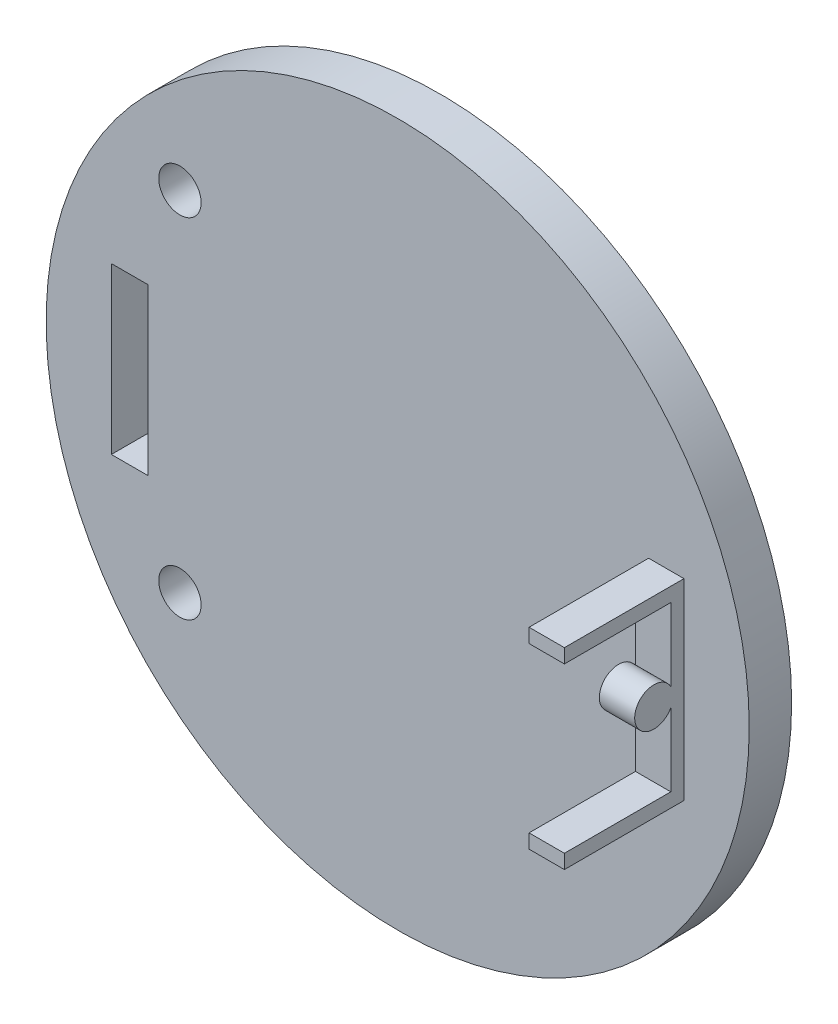
SolidWorks part; units mm, degrees
ref_plane "Front Plane" through (0, 0, 0) normal (0, 0, 1) x (1, 0, 0)
ref_plane "Top Plane" through (0, 0, 0) normal (0, 1, 0) x (1, 0, 0)
ref_plane "Right Plane" through (0, 0, 0) normal (1, 0, 0) x (0, 0, -1)
sketch "Sketch1" plane through (0, 0, 0) normal (0, 0, 1) x (1, 0, 0)
  line L0 (-1000, 0) -> (49000, 0) construction
  line L1 (17.755, 6.8) -> (20.255, 6.8)
  line L2 (17.755, 6.8) -> (17.755, -6.8)
  line L3 (17.755, -6.8) -> (20.255, -6.8)
  line L4 (20.255, 6.8) -> (20.255, -6.8)
  circle A0 centre (0, 0) radius 24.875
  point P7 (20.255, 0)
  point P10 (24.875, 0)
  dimension "D1" = 49.75
  dimension "D2" = 6.8
  dimension "D3" = 6.8
  dimension "D4" = 20.255
  dimension "D5" = 2.5
sketch "Sketch2" plane through (0, 0, 0) normal (0, 0, 1) x (1, 0, 0)
extrude "Boss-Extrude2" add sketch "Sketch1" against normal blind 3 contours A0
extrude "Boss-Extrude3" add sketch "Sketch1<4>" along normal blind 8.46 contours L2 L3 L4 L1
sketch "Sketch1<4>" plane through (0, 0, 0) normal (0, 0, 1) x (1, 0, 0) same geometry as "Sketch1"
sketch "Sketch4" plane through (20.255, 0, 0) normal (1, 0, 0) x (0, 0, -1)
  line L0 (0, 6.8) -> (0, 0.65)
  line L1 (0, 6.8) -> (0, -6.8) construction
  line L2 (0, -0.65) -> (0, -6.8)
  line L3 (0, 24.875) -> (0, -24.875) construction
  line L7 (0, 0.65) -> (-0.9313, 0.65) construction
  line L8 (-0.9313, 0.65) -> (-0.9313, -0.65) construction
  line L9 (-0.9313, -0.65) -> (0, -0.65) construction
  line L10 (-0.9313, 0.65) -> (0, 0.65)
  line L11 (-0.9313, -0.65) -> (0, -0.65)
  line L12 (0, 6.8) -> (-8.46, 6.8)
  line L13 (-8.46, 6.8) -> (-8.46, 5.8)
  line L14 (-8.46, 6.8) -> (-8.46, -6.8) construction
  line L15 (-8.46, 5.8) -> (-0.9313, 5.8)
  line L16 (-0.9313, 5.8) -> (-0.9313, 0.65)
  line L17 (-0.9313, -0.65) -> (-0.9313, -5.8)
  line L19 (-0.9313, -5.8) -> (-8.46, -5.8)
  line L20 (-8.46, -5.8) -> (-8.46, -6.8)
  line L21 (-8.46, -6.8) -> (0, -6.8)
  arc A4 (-0.9313, -0.65) -> (-0.9313, 0.65) centre (-2.1259, 0) cw
  point P15 (-0.9313, 0)
  line M8 (-8.46, 6.8) -> (-8.46, -6.8)
  dimension "D1" = 0.65
  dimension "D2" = 1.36
  dimension "D3" = 1
  dimension "D4" = 1
extrude "Cut-Extrude1" cut sketch "Sketch4" against normal up to surface (2.5 mm away) contours L17 A4 L16 L15 L19 M8 region at (20.255, 0, 4.8717) up to face at (17.755, 0, 4.23)
sketch "Sketch5" plane through (0, 0, 0) normal (0, 0, 1) x (1, 0, 0)
  line L1 (-20.26, 5.85) -> (-17.66, 5.85)
  line L2 (-20.26, 5.85) -> (-20.26, -5.85)
  line L3 (-20.26, -5.85) -> (-17.66, -5.85)
  line L4 (-17.66, 5.85) -> (-17.66, -5.85)
  point P4 (0, 0)
  dimension "D1" = 20.26
  dimension "D2" = 2.6
  dimension "D3" = 11.7
  dimension "D4" = 5.85
sketch "Sketch6" plane through (0, 0, 0) normal (0, 0, 1) x (1, 0, 0)
sketch "Sketch10" plane through (0, 0, 0) normal (0, 0, 1) x (1, 0, 0)
  circle A0 centre (-15.4092, 12.7514) radius 1.5
  circle A1 centre (-15.4092, -11.8993) radius 1.5
  dimension "D1" = 3
  dimension "D2" = 3
extrude "Cut-Extrude3" cut sketch "Sketch10" against normal blind 4.95
extrude "Cut-Extrude4" cut sketch "Sketch5" against normal blind 4.95
